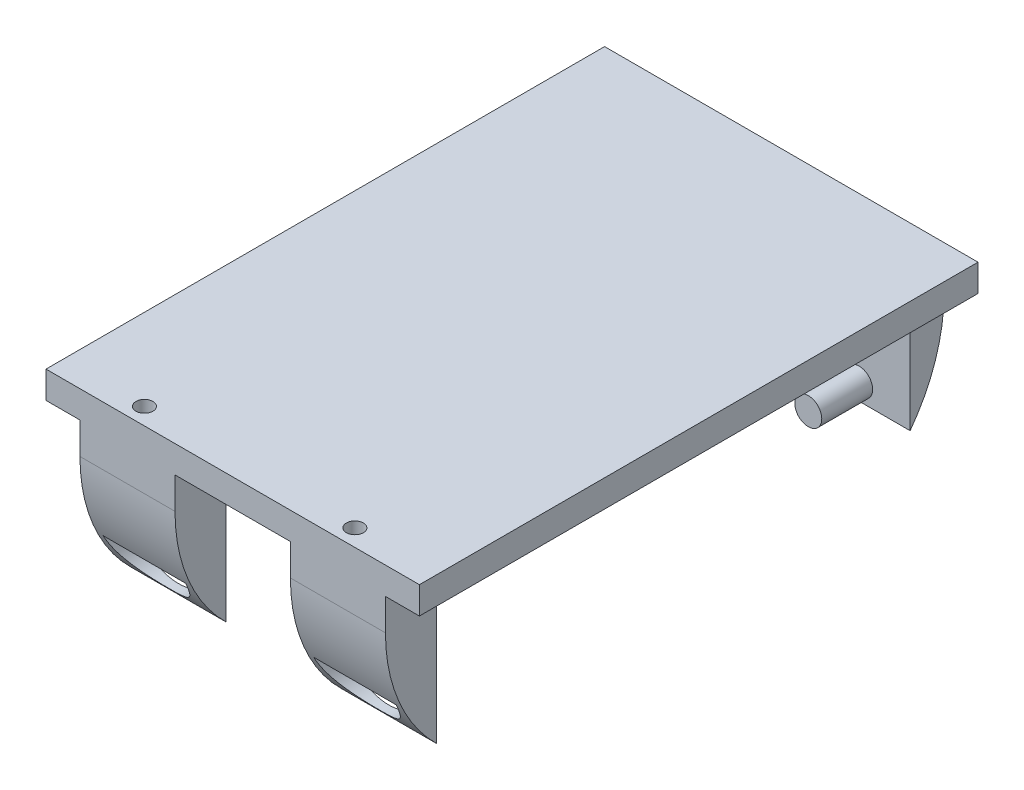
SolidWorks part; units mm, degrees
ref_plane "Спереди" through (0, 0, 0) normal (0, 0, 1) x (1, 0, 0)
ref_plane "Сверху" through (0, 0, 0) normal (0, 1, 0) x (1, 0, 0)
ref_plane "Справа" through (0, 0, 0) normal (1, 0, 0) x (0, 0, -1)
sketch "Эскиз1" plane through (0, 0, 0) normal (0, 0, 1) x (1, 0, 0)
  line L2 (-54.1538, 14.1538) -> (55.8462, 14.1538)
  line L3 (-54.1538, 14.1538) -> (-54.1538, 6.1538)
  line L4 (-54.1538, 6.1538) -> (55.8462, 6.1538)
  line L5 (55.8462, 14.1538) -> (55.8462, 6.1538)
  dimension "D1" = 110
  dimension "D2" = 8
extrude "Бобышка-Вытянуть1" add sketch "Эскиз1" along normal blind 164.55
sketch "Эскиз7" plane through (0, 6.1538, 0) normal (0, -1, 0) x (1, 0, 0)
  line L0 (-54.1538, 164.55) -> (55.8462, 164.55) construction
  line L1 (45.8462, 164.55) -> (17.8462, 164.55)
  line L2 (45.8462, 164.55) -> (45.8462, 149.55)
  line L3 (45.8462, 149.55) -> (17.8462, 149.55)
  line L4 (17.8462, 164.55) -> (17.8462, 149.55)
  dimension "D1" = 28
  dimension "D2" = 15
  dimension "D3" = 10
extrude "Бобышка-Вытянуть2" add sketch "Эскиз7" along normal blind 45
fillet "Скругление1" radius 50 1 edges at (31.8462, -38.8462, 164.55)
sketch "Эскиз10" plane through (0, 0, 149.55) normal (0, 0, -1) x (-1, 0, 0)
  line L0 (-17.8462, -38.8462) -> (-17.8462, 6.1538) construction
  line L1 (-17.8462, -38.8462) -> (-45.8462, -38.8462) construction
  circle A0 centre (-31.8462, -23.8462) radius 12.215
  dimension "D1" = 14
  dimension "D3" = 24.43
  dimension "D2" = 15
extrude "Вырез-Вытянуть3" cut sketch "Эскиз10" against normal blind 10
sketch "Эскиз11" plane through (0, 14.1538, 0) normal (0, 1, 0) x (1, 0, 0)
  line L0 (55.8462, -164.55) -> (55.8462, 0) construction
  line L1 (55.8462, -164.55) -> (-54.1538, -164.55) construction
  circle A0 centre (31.8462, -159.55) radius 2.5
  dimension "D1" = 24
  dimension "D3" = 5
  dimension "D2" = 5
extrude "Вырез-Вытянуть4" cut sketch "Эскиз11" against normal blind 30 contours A0
ref_plane "Плоскость1" through (0.8462, 0, 0) normal (-1, 0, 0) x (0, 0, 1)
mirror "Зеркальное отражение1" about plane through (0.8462, 0, 0) normal (-1, 0, 0) of "Вырез-Вытянуть4", "Вырез-Вытянуть3", "Скругление1", "Бобышка-Вытянуть2"
sketch "Эскиз13" plane through (0, 6.1538, 0) normal (0, -1, 0) x (-1, 0, 0)
  line L0 (54.1538, 0) -> (-55.8462, 0) construction
  line L1 (-45.8462, -10) -> (-17.8462, -10)
  line L2 (-45.8462, -10) -> (-45.8462, 0)
  line L3 (-45.8462, 0) -> (-17.8462, 0)
  line L4 (-17.8462, -10) -> (-17.8462, 0)
  dimension "D1" = 10
  dimension "D2" = 28
  dimension "D3" = 10
extrude "Бобышка-Вытянуть3" add sketch "Эскиз13" along normal blind 35
sketch "Эскиз14" plane through (0, 0, 10) normal (0, 0, 1) x (1, 0, 0)
  line L1 (17.8462, -28.8462) -> (17.8462, 6.1538) construction
  line L2 (45.8462, -28.8462) -> (17.8462, -28.8462) construction
  circle A0 centre (30.8462, -23.8462) radius 3.975
  dimension "D2" = 7.95
  dimension "D1" = 5
  dimension "D3" = 13
fillet "Скругление2" radius 50 1 edges at (31.8462, -28.8462, 0)
extrude "Бобышка-Вытянуть4" add sketch "Эскиз14" along normal blind 15 contours A0
mirror "Зеркальное отражение2" about plane through (0.8462, 0, 0) normal (-1, 0, 0) of "Скругление2", "Бобышка-Вытянуть3", "Бобышка-Вытянуть4"
